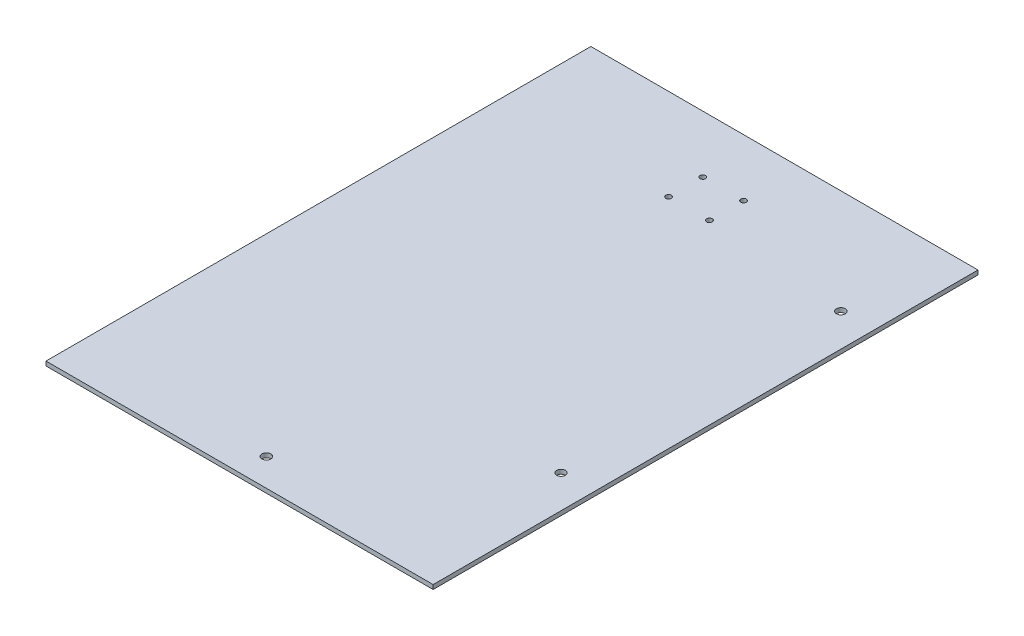
SolidWorks part; units mm, degrees
material "2024-T361"
ref_plane "Front Plane" through (0, 0, 0) normal (0, 0, 1) x (1, 0, 0)
ref_plane "Top Plane" through (0, 0, 0) normal (0, 1, 0) x (1, 0, 0)
ref_plane "Right Plane" through (0, 0, 0) normal (1, 0, 0) x (0, 0, -1)
sketch "Sketch1" plane through (0, 0, 0) normal (0, 0, 1) x (1, 0, 0)
  line L0 (5, -60) -> (5, 85) construction
  line L1 (5, 45) -> (275, 45)
  line L2 (5, 45) -> (5, 48)
  line L3 (5, 48) -> (275, 48)
  line L4 (275, 45) -> (275, 48)
  line L5 (275, -60) -> (275, 85) construction
  line L7 (3, -65) -> (277, -65) construction
  dimension "D1" = 3
  dimension "D2" = 110
extrude "Boss-Extrude1" add sketch "Sketch1" along normal blind 380
sketch "Sketch6" plane through (0, 45, 0) normal (0, -1, 0) x (1, 0, 0)
  circle A0 centre (122.9011, 39.847) radius 1.9331
  circle A1 centre (122.9011, 63.6657) radius 1.9376
  circle A2 centre (151.3623, 39.847) radius 1.9381
  circle A3 centre (151.3623, 63.6657) radius 1.9625
extrude "Cut-Extrude1" cut sketch "Sketch6" against normal up to next
sketch "Sketch7" plane through (0, 48, 0) normal (0, 1, 0) x (1, 0, 0)
  circle A0 centre (252.1123, -267.8897) radius 3.0185
  circle A1 centre (252.1123, -72.7488) radius 3.0894
  circle A2 centre (139.4673, -360.7759) radius 3.1062
extrude "Cut-Extrude2" cut sketch "Sketch7" against normal up to next
